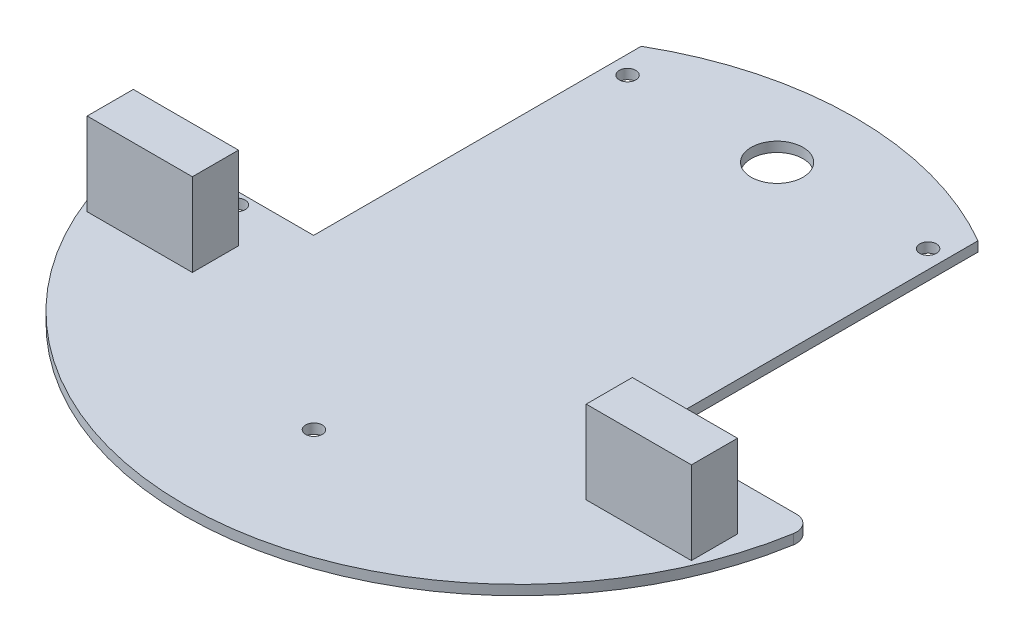
SolidWorks part; units mm, degrees
material "ABS"
ref_plane "Front Plane" through (0, 0, 0) normal (0, 0, 1) x (1, 0, 0)
ref_plane "Top Plane" through (0, 0, 0) normal (0, 1, 0) x (1, 0, 0)
ref_plane "Right Plane" through (0, 0, 0) normal (1, 0, 0) x (0, 0, -1)
sketch "Sketch1" plane through (0, 0, 0) normal (0, 1, 0) x (1, 0, 0)
  line L1 (-18, -10) -> (18, -10)
  line L2 (-18, -10) -> (-18, 10)
  line L3 (-18, 10) -> (18, 10)
  line L4 (18, -10) -> (18, 10)
  line L5 (-18, -10) -> (18, 10) construction
  line L6 (-18, 10) -> (18, -10) construction
  point P0 (0, 0)
  dimension "D1" = 36
  dimension "D2" = 20
extrude "Boss-Extrude1" add sketch "Sketch1" along normal blind 1.9
sketch "Sketch3" plane through (0, 0, 0) normal (0, -1, 0) x (1, 0, 0)
  line L0 (0, 0) -> (0, 52.4373) construction
  line L1 (37.5, -26.7252) -> (-37.5, -26.7252) construction
  line L2 (37.5, -26.7252) -> (32.5, -26.7252)
  line L3 (0, 0) -> (0, -36.2287) construction
  line L4 (-37.5, -26.7252) -> (-32.5, -26.7252)
  line L5 (32.5, -26.7252) -> (32.5, 33.2748)
  line L6 (-32.5, -26.7252) -> (-32.5, 33.2748)
  line L7 (32.5, 33.2748) -> (60.6723, 33.2748)
  line L9 (-32.5, 33.2748) -> (-60.6723, 33.2748)
  arc A0 (37.5, -26.7252) -> (-37.5, -26.7252) centre (0, 26.2187) cw
  arc A1 (-34.4895, -37.0634) -> (34.4895, -37.0634) centre (0, 26.2187) ccw construction
  arc A2 (68.1909, 19.7187) -> (51.8431, 70.9907) centre (0, 26.2187) ccw construction
  arc A3 (63.6319, 36.7654) -> (-63.6319, 36.7654) centre (0, 26.2187) ccw
  circle A4 centre (0, 26.2187) radius 72.5 construction
  arc A5 (-60.6723, 33.2748) -> (-63.6319, 36.7654) centre (-60.6723, 36.2748) cw
  arc A6 (60.6723, 33.2748) -> (63.6319, 36.7654) centre (60.6723, 36.2748) ccw
  point P7 (0, 26.2187)
  point P20 (-64.1129, 33.2748)
  point P26 (64.1129, 33.2748)
  dimension "D1" = 4
  dimension "D3" = 5
  dimension "D4" = 60
  dimension "D5" = 3
  dimension "D6" = 7.0562
  dimension "D2" = 65
extrude "Boss-Extrude2" add sketch "Sketch3" against normal blind 1.9
sketch "Sketch4" plane through (0, 1.9, 0) normal (0, 1, 0) x (1, 0, 0)
  line L0 (-32.5, 26.7252) -> (-32.5, 34.1947)
  line L1 (-32.5, 34.1947) -> (-40.4421, 34.1947)
  line L2 (-40.4421, 34.1947) -> (-37.5, 26.7252)
  line L3 (-37.5, 26.7252) -> (-32.5, 26.7252)
  line L4 (0, 0) -> (0, 49.3906) construction
  line L5 (37.5, 26.7252) -> (32.5, 26.7252)
  line L6 (40.4421, 34.1947) -> (37.5, 26.7252)
  line L7 (32.5, 34.1947) -> (40.4421, 34.1947)
  line L8 (32.5, 26.7252) -> (32.5, 34.1947)
  arc A0 (37.5, 26.7252) -> (-37.5, 26.7252) centre (0, -26.2187) ccw construction
extrude "Cut-Extrude1" cut sketch "Sketch4" against normal blind 10
sketch "Sketch5" plane through (0, 1.9, 0) normal (0, 1, 0) x (1, 0, 0)
  line L0 (0, 0) -> (0, 38.6605) construction
  circle A0 centre (0, 23.6605) radius 5
  arc A1 (32.5, 29.9334) -> (-32.5, 29.9334) centre (0, -26.2187) ccw construction
  dimension "D1" = 10
  dimension "D2" = 15
extrude "Cut-Extrude2" cut sketch "Sketch5" against normal up to surface (1.9 mm away) up to face at (0, 0, 23.8273)
sketch "Sketch6" plane through (0, 1.9, 0) normal (0, 1, 0) x (1, 0, 0)
  line L0 (0, 38.6605) -> (0, -90.7187) construction
  line L1 (-45, -35.5743) -> (45, -35.5743) construction
  line L2 (-29, 23.8048) -> (29, 23.8048) construction
  line L3 (-45, -31.5743) -> (-45, -49.6893) construction
  line L4 (-50, -31.5743) -> (-40, -31.5743) construction
  arc A0 (32.5, 29.9334) -> (-32.5, 29.9334) centre (0, -26.2187) ccw construction
  arc A1 (-63.6319, -36.7654) -> (63.6319, -36.7654) centre (0, -26.2187) ccw construction
  circle A2 centre (0, -65.7187) radius 1.6
  circle A3 centre (-45, -35.5743) radius 1.6
  circle A4 centre (45, -35.5743) radius 1.6
  circle A5 centre (-29, 23.8048) radius 1.6
  circle A6 centre (29, 23.8048) radius 1.6
  dimension "D1" = 25
  dimension "D2" = 3.2
  dimension "D3" = 4
  dimension "D5" = 58
extrude "Cut-Extrude3" cut sketch "Sketch6" against normal up to surface (1.9 mm away) up to face at (0, 0, -28.6605)
sketch "Esquisse1" plane through (0, 1.9, 0) normal (0, 1, 0) x (1, 0, 0)
  line L0 (0, 0) -> (0, -58.0938) construction
  line L1 (58.3, -42.2748) -> (38, -42.2748)
  line L2 (58.3, -42.2748) -> (58.3, -51.1748)
  line L3 (58.3, -51.1748) -> (38, -51.1748)
  line L4 (38, -42.2748) -> (38, -51.1748)
  line L5 (-38, -42.2748) -> (-38, -51.1748)
  line L6 (-58.3, -51.1748) -> (-38, -51.1748)
  line L7 (-58.3, -42.2748) -> (-58.3, -51.1748)
  line L8 (-58.3, -42.2748) -> (-38, -42.2748)
  line L10 (32.5, -33.2748) -> (60.6723, -33.2748) construction
  dimension "D1" = 20.3
  dimension "D2" = 38
  dimension "D3" = 9
  dimension "D4" = 8.9
extrude "Boss.-Extru.1" add sketch "Esquisse1" along normal blind 16
